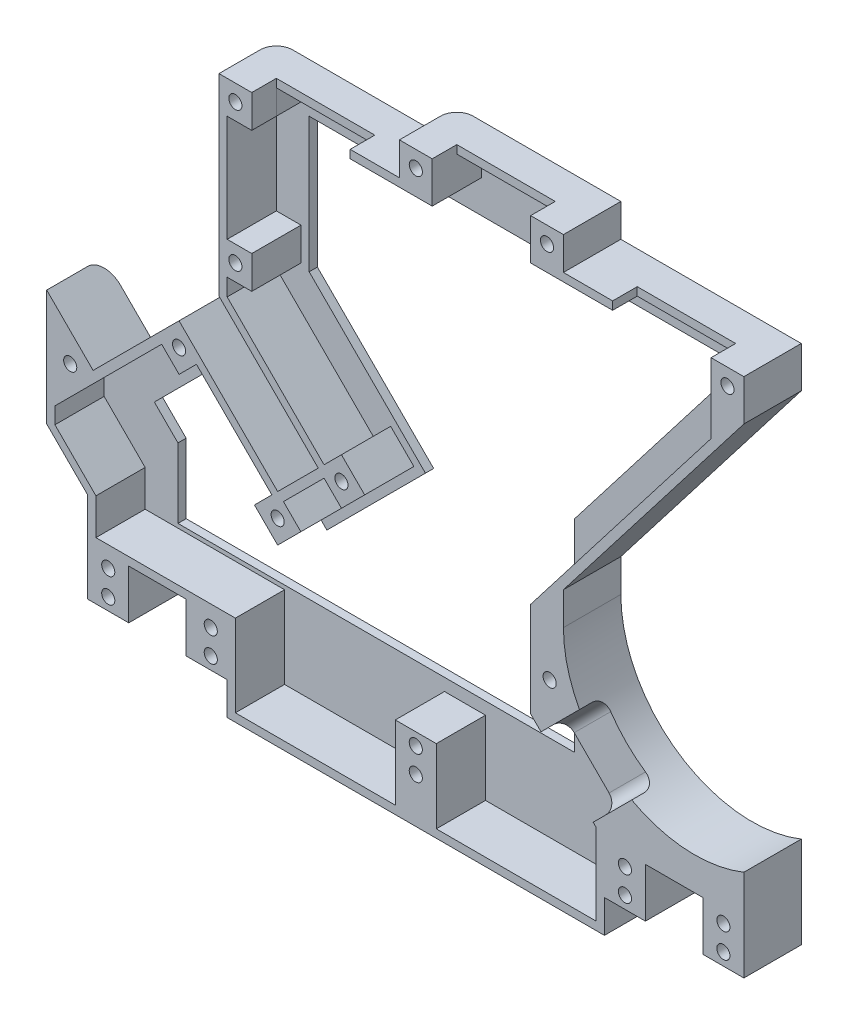
SolidWorks part; units mm, degrees
ref_plane "Front" through (0, 0, 0) normal (0, 0, 1) x (1, 0, 0)
ref_plane "Top" through (0, 0, 0) normal (0, 1, 0) x (1, 0, 0)
ref_plane "Right" through (0, 0, 0) normal (1, 0, 0) x (0, 0, -1)
sketch "Sketch1" plane through (0, 0, 0) normal (0, 0, 1) x (1, 0, 0)
  line L0 (21, 67.5) -> (21, 43.9999)
  line L1 (85, 15.1676) -> (85, 10)
  line L4 (21, 67.5) -> (43, 67.5)
  line L5 (63, 71.5) -> (63, 67.5)
  line L6 (43, 67.5) -> (43, 71.5)
  line L8 (5, 10) -> (5, 15)
  line L9 (43, 71.5) -> (63, 71.5)
  line L10 (0, 34.1421) -> (0, 20)
  line L11 (63, 67.5) -> (85, 67.5)
  line L13 (0, 20) -> (5, 15)
  line L20 (5.6569, 28.4853) -> (0, 34.1421)
  line L22 (22, 10) -> (5, 10)
  line L23 (16.136, 38.9644) -> (5.6569, 28.4853)
  line L25 (28.1568, 26.9436) -> (16.136, 38.9644)
  line L28 (68, 0) -> (22, 0)
  line L31 (21, 43.9999) -> (33.1066, 31.8933)
  line L34 (22, 0) -> (22, 10)
  line L35 (68, 10) -> (68, 0)
  line L36 (85, 10) -> (68, 10)
  line L43 (33.1066, 31.8933) -> (28.1568, 26.9436)
  line L50 (22, 0) -> (0, 0) construction
  line L56 (63, 34) -> (85, 62.5)
  line L58 (85, 67.5) -> (85, 62.5)
  line L59 (63, 34) -> (63, 30)
  arc A11 (63, 30) -> (85, 15.1676) centre (79, 30) ccw
extrude "Boss-Extrude1" add sketch "Sketch1" along normal blind 1 contours L31 L43 L25 L23 L20 L10 L13 L8 L22 L34 L28 L35 L36 L9 L6 L4 L0 region at (43.6817, 34.5668, 0)
sketch "Sketch4" plane through (0, 0, 0) normal (0, 0, 1) x (1, 0, 0)
  line L0 (21, 67.5) -> (21, 43.9999)
  line L1 (21, 67.5) -> (43, 67.5)
  line L2 (63, 67.5) -> (85, 67.5)
  line L3 (43, 67.5) -> (43, 71.5)
  line L4 (5, 4) -> (5, 15)
  line L5 (43, 71.5) -> (63, 71.5)
  line L6 (0, 34.1421) -> (0, 20)
  line L7 (63, 71.5) -> (63, 67.5)
  line L8 (0, 20) -> (5, 15)
  line L9 (63, 34) -> (63, 30)
  line L10 (5.6569, 28.4853) -> (0, 34.1421)
  line L11 (31, 65.4999) -> (23, 65.4999) construction
  line L12 (16.136, 38.9644) -> (5.6569, 28.4853)
  line L13 (28.1568, 26.9436) -> (16.136, 38.9644)
  line L14 (68, 0) -> (22, 0)
  line L15 (21, 43.9999) -> (33.1066, 31.8933)
  line L16 (25, 66.5) -> (47, 66.5)
  line L17 (73, 10) -> (80, 10)
  line L18 (53, 69.4999) -> (45, 69.4999) construction
  line L19 (33.1066, 31.8933) -> (28.1568, 26.9436)
  line L20 (22, 0) -> (0, 0) construction
  line L21 (85, 10) -> (85, 4)
  line L22 (85, 4) -> (80, 4)
  line L23 (80, 4) -> (80, 10)
  line L24 (5, 4) -> (10, 4)
  line L25 (73, 10) -> (73, 4)
  line L26 (73, 4) -> (68, 4)
  line L27 (68, 4) -> (68, 0)
  line L28 (10, 4) -> (10, 10)
  line L29 (10, 10) -> (17, 10)
  line L30 (17, 10) -> (17, 4)
  line L31 (17, 4) -> (22, 4)
  line L32 (22, 4) -> (22, 0)
  line L33 (53, 69.4999) -> (61, 69.4999) construction
  line L34 (85, 15.1676) -> (85, 10)
  line L35 (59, 18.8873) -> (67, 10.8873)
  line L36 (16.136, 38.9644) -> (17.5502, 37.5502) construction
  line L37 (33.1066, 31.8933) -> (34.5208, 30.4791) construction
  line L38 (67, 10.8873) -> (67, 1)
  line L39 (17.5502, 37.5502) -> (16.136, 36.136) construction
  line L40 (31, 55.4999) -> (31, 65.4999) construction
  line L41 (31, 55.4999) -> (31, 48.4999) construction
  line L42 (31, 48.4999) -> (23, 48.4999) construction
  line L43 (82.5, 3.9999) -> (82.5, 5.4999) construction
  line L44 (28.1568, 26.9436) -> (29.571, 25.5294) construction
  line L45 (82.5, 5.4999) -> (82.5, 8.4999) construction
  line L46 (7.5, 3.9999) -> (7.5, 5.4999) construction
  line L47 (29.571, 25.5294) -> (28.1568, 24.1152) construction
  line L48 (34.5208, 30.4791) -> (35.935, 31.8933) construction
  line L49 (70.5, 3.9999) -> (70.5, 5.4999) construction
  line L50 (70.5, 5.4999) -> (70.5, 8.4999) construction
  line L51 (7.5, 5.4999) -> (7.5, 8.4999) construction
  line L52 (45, 9.9999) -> (45, 8.4999) construction
  line L53 (20, 3.9999) -> (20, 5.4999) construction
  line L54 (20, 5.4999) -> (20, 8.4999) construction
  line L55 (45, 8.4999) -> (45, 5.4999) construction
  line L56 (6.364, 27.7782) -> (2.864, 27.7782) construction
  line L58 (25, 63.5) -> (25, 66.5)
  line L59 (25, 63.5) -> (22, 63.5)
  line L60 (81, 58.9547) -> (59, 30.4547)
  line L61 (59, 66.5) -> (81, 66.5)
  line L63 (85, 67.5) -> (85, 62.5)
  line L64 (47, 66.5) -> (47, 70.5)
  line L65 (47, 70.5) -> (59, 70.5)
  line L66 (59, 70.5) -> (59, 66.5)
  line L68 (81, 58.9547) -> (81, 66.5)
  line L70 (59, 30.4547) -> (59, 18.8873)
  line L71 (67, 1) -> (47.5, 1)
  line L72 (47.5, 1) -> (47.5, 9.9999)
  line L73 (47.5, 9.9999) -> (42.5, 9.9999)
  line L74 (42.5, 9.9999) -> (42.5, 1)
  line L75 (42.5, 1) -> (23, 1)
  line L76 (23, 1) -> (23, 11)
  line L77 (23, 11) -> (6, 11)
  line L78 (22, 50.4999) -> (25, 50.4999)
  line L79 (25, 50.4999) -> (25, 46.4999)
  line L80 (22, 50.4999) -> (22, 63.5)
  line L81 (25, 46.4999) -> (22, 46.4999)
  line L82 (22, 46.4999) -> (22, 44.4141)
  line L83 (22, 44.4141) -> (33.8137, 32.6004)
  line L84 (38.7634, 31.8933) -> (35.935, 29.0649)
  line L85 (35.935, 34.7218) -> (38.7634, 31.8933)
  line L86 (35.935, 34.7218) -> (33.8137, 32.6004)
  line L87 (35.935, 29.0649) -> (33.8137, 31.1862)
  line L88 (33.8137, 31.1862) -> (28.8639, 26.2365)
  line L89 (28.8639, 26.2365) -> (30.9852, 24.1152)
  line L90 (30.9852, 24.1152) -> (28.1568, 21.2867)
  line L91 (28.1568, 21.2867) -> (25.3284, 24.1152)
  line L92 (25.3284, 24.1152) -> (27.4497, 26.2365)
  line L93 (27.4497, 26.2365) -> (18.2573, 35.4289)
  line L94 (18.2573, 35.4289) -> (16.136, 33.3075)
  line L95 (16.136, 33.3075) -> (14.0147, 35.4289)
  line L96 (1, 20.4142) -> (6, 15.4142)
  line L98 (6, 15.4142) -> (6, 11)
  line L100 (1, 22.4142) -> (14.0147, 35.4289)
  line L101 (1, 20.4142) -> (1, 22.4142)
  line L121 (63, 34) -> (85, 62.5)
  arc A2 (63, 30) -> (85, 15.1676) centre (79, 30) ccw
extrude "Boss-Extrude3" add sketch "Sketch4" along normal blind 7
fillet "Fillet1" radius 2 5 edges at (5, 9.5, 0) (2.5, 17.5, 0) (0, 27.0711, 0) (21, 55.7499, 0) (43, 69.5, 0)
sketch "Sketch5" plane through (0, 0, 0) normal (0, 0, 1) x (1, 0, 0)
  line L0 (67.6863, 18.6863) -> (66.9792, 17.9792) construction
  line L1 (83, 67.5) -> (83, 65.5) construction
  line L3 (66.9792, 17.9792) -> (61.3223, 23.636) construction
  line L4 (31, 65.4999) -> (23, 65.4999) construction
  line L6 (53, 69.4999) -> (45, 69.4999) construction
  line L8 (53, 69.4999) -> (61, 69.4999) construction
  line L12 (75, 65.4999) -> (75, 48.7499) construction
  line L16 (16.136, 38.9644) -> (17.5502, 37.5502) construction
  line L33 (75, 48.7499) -> (75, 31.9999) construction
  line L34 (17.5502, 37.5502) -> (16.136, 36.136) construction
  line L35 (31, 55.4999) -> (31, 65.4999) construction
  line L38 (31, 55.4999) -> (31, 48.4999) construction
  line L39 (31, 48.4999) -> (23, 48.4999) construction
  line L40 (82.5, 3.9999) -> (82.5, 5.4999) construction
  line L41 (28.1568, 26.9436) -> (29.571, 25.5294) construction
  line L42 (82.5, 5.4999) -> (82.5, 8.4999) construction
  line L43 (7.5, 3.9999) -> (7.5, 5.4999) construction
  line L44 (29.571, 25.5294) -> (28.1568, 24.1152) construction
  line L46 (70.5, 3.9999) -> (70.5, 5.4999) construction
  line L47 (70.5, 5.4999) -> (70.5, 8.4999) construction
  line L49 (7.5, 5.4999) -> (7.5, 8.4999) construction
  line L51 (45, 9.9999) -> (45, 8.4999) construction
  line L52 (20, 3.9999) -> (20, 5.4999) construction
  line L53 (20, 5.4999) -> (20, 8.4999) construction
  line L54 (45, 8.4999) -> (45, 5.4999) construction
  line L55 (6.364, 27.7782) -> (2.864, 27.7782) construction
  circle A0 centre (35.935, 31.8933) radius 0.8
  circle A1 centre (83, 65.5) radius 0.8
  circle A2 centre (61.3223, 23.636) radius 0.8
  circle A14 centre (23, 65.4999) radius 0.8
  circle A15 centre (45, 69.4999) radius 0.8
  circle A16 centre (61, 69.4999) radius 0.8
  circle A18 centre (16.136, 36.136) radius 0.8
  circle A19 centre (28.1568, 24.1152) radius 0.8
  circle A20 centre (23, 48.4999) radius 0.8
  circle A23 centre (45, 8.4999) radius 0.8
  circle A24 centre (82.5, 5.4999) radius 0.8
  circle A25 centre (82.5, 8.4999) radius 0.8
  circle A26 centre (70.5, 5.4999) radius 0.8
  circle A27 centre (70.5, 8.4999) radius 0.8
  circle A28 centre (7.5, 5.4999) radius 0.8
  circle A29 centre (7.5, 8.4999) radius 0.8
  circle A30 centre (20, 5.4999) radius 0.8
  circle A31 centre (20, 8.4999) radius 0.8
  circle A33 centre (45, 5.4999) radius 0.8
  circle A34 centre (2.864, 27.7782) radius 0.8
extrude "Screw Holes" cut sketch "Sketch5" along normal through all
sketch "Sketch6" plane through (0, 0, 0) normal (0, 0, 1) x (1, 0, 0)
  line L0 (59, 67.5) -> (59, 71.5)
  line L2 (25, 67.5) -> (37, 67.5)
  line L3 (69, 67.5) -> (81, 67.5)
  line L4 (47, 67.5) -> (59, 67.5)
  line L5 (47, 71.5) -> (47, 67.5)
  line L6 (81, 67.5) -> (81, 63.5001)
  line L7 (81, 63.5001) -> (69, 63.5001)
  line L8 (37, 67.5) -> (37, 63.5001)
  line L9 (69, 63.5001) -> (69, 67.5)
  line L11 (59, 71.5) -> (47, 71.5)
  line L13 (37, 63.5001) -> (24.9999, 63.5001)
  line L14 (24.9999, 63.5001) -> (25, 67.5)
extrude "Tube Openings - Finger" cut sketch "Sketch6" against normal blind 3 from offset 7
sketch "Sketch9" plane through (38.9437, 38.9437, 0) normal (-0.7071, -0.7071, 0) x (0, 0, 1)
  line L0 (7, -30.1482) -> (5.5, -30.1482)
  line L1 (4, -31.6482) -> (4, -37.6482)
  line L3 (7, -39.1482) -> (7, -30.1482)
  line L4 (5.5, -30.1482) -> (5.5, -31.6482) construction
  line L5 (7, -39.1482) -> (5.5, -39.1482)
  line L6 (5.5, -39.1482) -> (5.5, -37.6482) construction
  arc A0 (5.5, -30.1482) -> (4, -31.6482) centre (5.5, -31.6482) ccw
  arc A1 (5.5, -39.1482) -> (4, -37.6482) centre (5.5, -37.6482) cw
extrude "Tube Openings - Thumb" cut sketch "Sketch9" against normal blind 7
sketch "Sketch10" plane through (0, 0, 0) normal (0, 0, 1) x (1, 0, 0)
  line L2 (58.3223, 11.4999) -> (10, 11.4999)
  line L3 (28.1568, 19.8725) -> (16.136, 31.8933)
  line L4 (40.1776, 31.8933) -> (28.1568, 19.8725)
  line L5 (58.3223, 36.1229) -> (78.6836, 62.5)
  line L6 (10, 20) -> (7.1213, 22.8787)
  line L7 (10, 11.4999) -> (10, 20)
  line L9 (58.3223, 11.4999) -> (58.3223, 36.1229)
  line L10 (7.1213, 22.8787) -> (16.136, 31.8933)
  line L11 (78.6836, 62.5) -> (26, 62.5)
  line L13 (26, 46.071) -> (26, 62.5)
  line L14 (40.1776, 31.8933) -> (26, 46.071)
extrude "Cut-Extrude1" cut sketch "Sketch10" along normal through all
